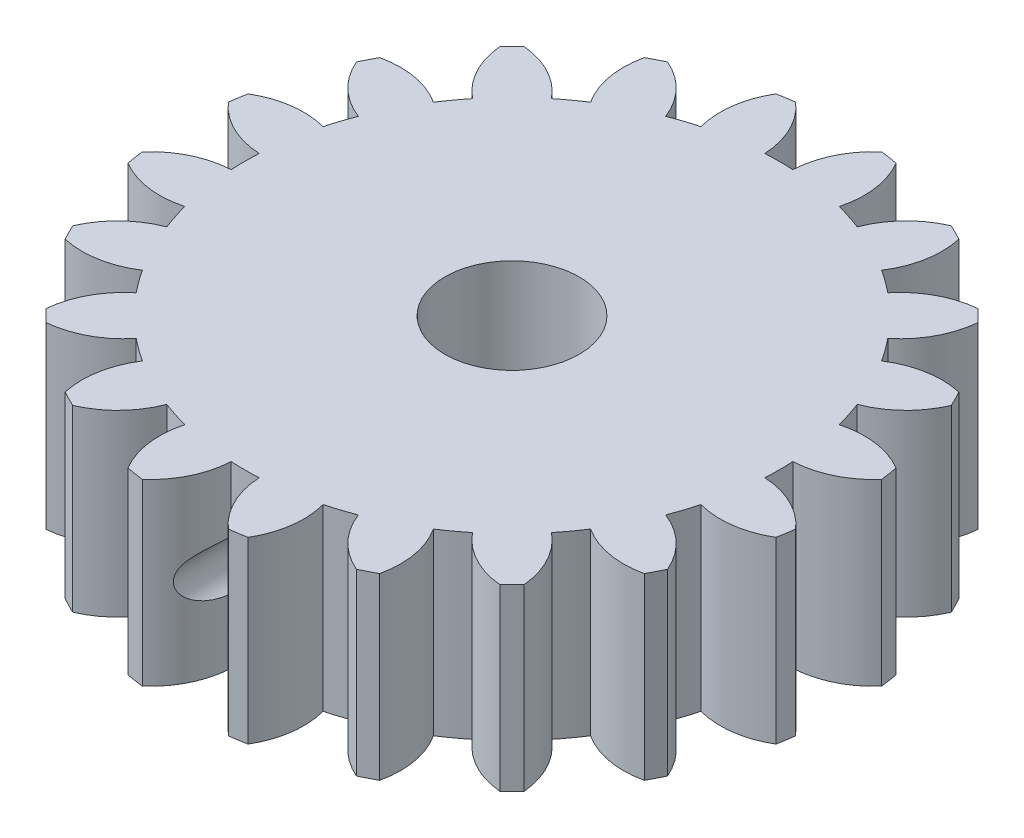
SolidWorks part; units mm, degrees
ref_plane "Front Plane" through (0, 0, 0) normal (0, 0, 1) x (1, 0, 0)
ref_plane "Top Plane" through (0, 0, 0) normal (0, 1, 0) x (1, 0, 0)
ref_plane "Right Plane" through (0, 0, 0) normal (1, 0, 0) x (0, 0, -1)
sketch "Sketch1" plane through (0, 0, 0) normal (0, 1, 0) x (1, 0, 0)
  circle A0 centre (0, 0) radius 23.368
extrude "Boss-Extrude1" add sketch "Sketch1" along normal blind 12.7
hole_wizard "3/8 (0.375) Diameter Hole1" positions "Sketch4" profile "Sketch5" hole size "3/8" standard "ANSI Inch" end condition through all
sketch "Sketch4" plane through (0, 12.7, 0) normal (0, 1, 0) x (1, 0, 0)
  point P0 (0, 0)
sketch "Sketch5" plane through (0, 12.7, 0) normal (1, 0, 0) x (0, 0, 1)
  line L0 (0, 0) -> (0, 12.7)
  line L1 (0, 12.7) -> (4.7625, 12.7)
  line L2 (4.7625, 12.7) -> (4.7625, 0)
  line L5 (4.7625, 0) -> (0, 0)
  line L11 (0, -6.35) -> (0, 107.95) construction
  dimension "Thru Hole Dia." = 9.525
  dimension "Thru Hole Depth" = 12.7
sketch "Sketch6" plane through (0, 12.7, 0) normal (0, 1, 0) x (1, 0, 0)
  line L0 (0, -8.0769) -> (0, 48.8756) construction
  line L1 (-0.9917, 18.9224) -> (-1.5375, 18.8938) construction
  line L2 (-0.9917, 18.9224) -> (-0.9682, 18.4735) construction
  circle A0 centre (0, 0) radius 23.368 construction
  circle A1 centre (0, 0) radius 23.368 construction
  arc A2 (-3.0501, 23.1681) -> (3.0501, 23.1681) centre (0, 0) cw
  arc A3 (-0.9917, 18.9224) -> (0.9917, 18.9224) centre (0, 0) cw
  arc A4 (-0.9917, 18.9224) -> (-3.0501, 23.1681) centre (-7.0547, 18.6047) ccw
  arc A5 (0.9917, 18.9224) -> (3.0501, 23.1681) centre (7.0547, 18.6047) cw
  point P10 (0, 23.368)
  point P11 (0, 18.9484)
  dimension "D2" = 15
  dimension "D3" = 18.9484
  dimension "D1" = 6
extrude "Cut-Extrude1" cut sketch "Sketch6" against normal through all
pattern_circular "CirPattern1" count 20 every 18 about axis through (0, 12.7, 0) along (0, 1, 0) of "Cut-Extrude1"
ref_plane "Plane2" through (0, 0, 23.1681) normal (0, 0, 1) x (1, 0, 0)
hole_wizard "#10-32 Tapped Hole2" positions "Sketch8" profile "Sketch9" tap size "#10-32" standard "ANSI Inch" end condition up to next
sketch "Sketch8" plane through (0, 0, 23.1681) normal (0, 0, 1) x (1, 0, 0)
  line L0 (0, 0) -> (0, 12.7) construction
  line L2 (0.9917, 12.7) -> (-0.9917, 12.7) construction
  line L3 (0.9917, 12.7) -> (-0.9917, 12.7) construction
  point P0 (0, 6.35)
  point P14 (0, 6.35)
sketch "Sketch9" plane through (0, 6.35, 23.1681) normal (1, 0, 0) x (0, -1, 0)
  line L0 (0, 0) -> (0, 18.4056)
  line L1 (0, 18.4056) -> (2.0193, 18.4056)
  line L2 (2.0193, 18.4056) -> (2.0193, 0)
  line L5 (2.0193, 0) -> (0, 0)
  line L11 (0, -6.35) -> (0, 107.95) construction
  dimension "Thru Tap Drill Dia." = 4.0386
  dimension "Thru Tap Drill Depth" = 18.4056
cosmetic thread "Hole Thread2" parameters "D2"=4.826
